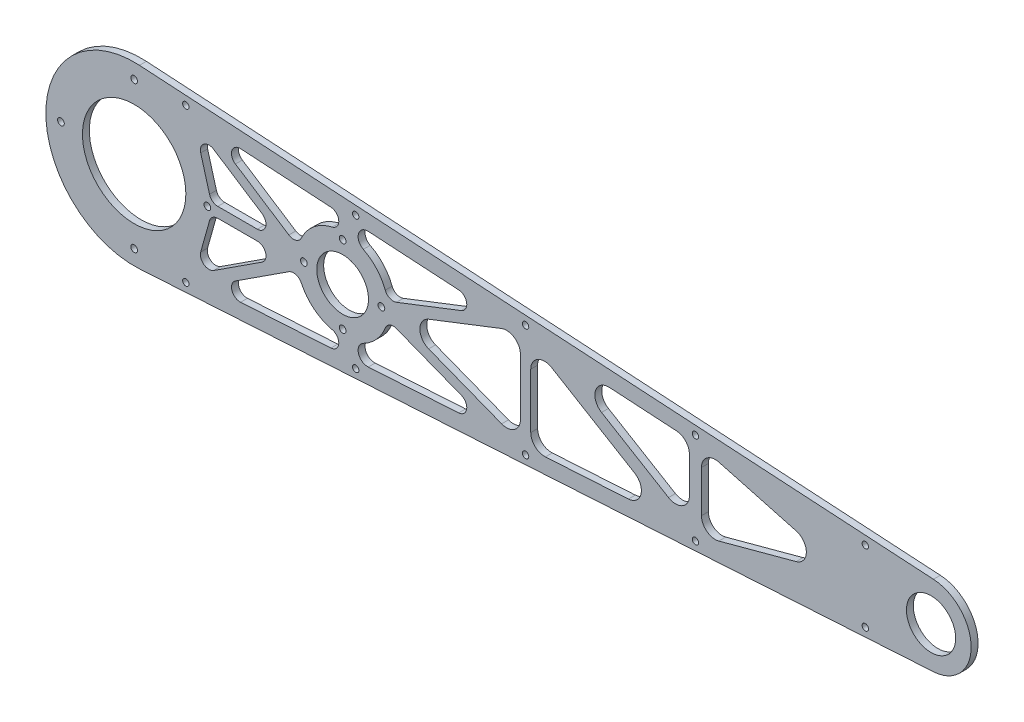
SolidWorks part; units mm, degrees
ref_plane "Front Plane" through (0, 0, 0) normal (0, 0, 1) x (1, 0, 0)
ref_plane "Top Plane" through (0, 0, 0) normal (0, 1, 0) x (1, 0, 0)
ref_plane "Right Plane" through (0, 0, 0) normal (1, 0, 0) x (0, 0, -1)
sketch "Sketch1" plane through (0, 0, 0) normal (0, 0, 1) x (1, 0, 0)
  line L0 (-231.25, 0) -> (231.25, 0) construction
  line L1 (-228.1515, 51.1562) -> (232.6579, 23.2449)
  line L2 (-228.1515, -51.1562) -> (232.6579, -23.2449)
  line L3 (191.25, 20.7438) -> (-201.25, 44.5177) construction
  circle A0 centre (231.25, 0) radius 14.2875
  arc A1 (232.6579, 23.2449) -> (232.6579, -23.2449) centre (231.25, 0) cw
  circle A2 centre (-231.25, 0) radius 42.5 construction
  circle A3 centre (-110.25, 0) radius 22.5 construction
  arc A4 (-228.1515, 51.1562) -> (-228.1515, -51.1562) centre (-231.25, 0) ccw
  circle A5 centre (-231.25, 42.5) radius 1.75 construction
  circle A6 centre (-231.25, 0) radius 30
  circle A7 centre (-110.25, 0) radius 15
  circle A8 centre (231.25, 0) radius 35.306 construction
  circle A9 centre (-201.25, 44.5177) radius 1.85
  circle A10 centre (-102.6633, 38.5462) radius 1.85
  circle A11 centre (-4.0767, 32.5748) radius 1.85
  circle A12 centre (94.51, 26.6034) radius 1.85
  circle A13 centre (193.0966, 20.632) radius 1.85
  circle A14 centre (291.6833, 14.6606) radius 1.85 construction
  circle A15 centre (193.0966, -20.632) radius 1.85
  circle A16 centre (94.51, -26.6034) radius 1.85
  circle A17 centre (-4.0767, -32.5748) radius 1.85
  circle A18 centre (-102.6633, -38.5462) radius 1.85
  circle A19 centre (-201.25, -44.5177) radius 1.85
  point P4 (0, 0)
  point P15 (-231.25, 44.25)
  point P16 (-273.75, 0)
  point P17 (-231.25, 51.25)
  point P18 (-110.25, 22.5)
  point P19 (-231.25, -42.5)
  point P20 (-188.75, 0)
  point P21 (-132.75, 0)
  point P22 (-110.25, -22.5)
  point P23 (-87.75, 0)
  dimension "D2" = 28.575
  dimension "D3" = 85
  dimension "D5" = 45
  dimension "D6" = 3.5
  dimension "D7" = 7
  dimension "D8" = 9
  dimension "D9" = 60
  dimension "D10" = 30
  dimension "D11" = 70.612
  dimension "D13" = 3.7
  dimension "D16" = 6
  dimension "D1" = 462.5
  dimension "D4" = 121
  dimension "D12" = 5
  dimension "D14" = 30
  dimension "D15" = 40
extrude "Boss-Extrude1" add sketch "Sketch1" along normal blind 4
sketch "Sketch4" plane through (0, 0, 4) normal (0, 0, 1) x (1, 0, 0)
  point P0 (-231.25, 42.5)
  point P7 (-188.75, 0)
  point P10 (-132.75, 0)
  point P13 (-110.25, 22.5)
  point P16 (-87.75, 0)
  point P19 (-110.25, -22.5)
  point P24 (-273.75, 0)
  point P28 (-231.25, -42.5)
hole_wizard "M3.5 Clearance Hole1" positions "Sketch4" profile "Sketch6" hole size "M3.5" standard "ANSI Metric" end condition up to next
sketch "Sketch6" plane through (-231.25, 42.5, 4) normal (1, 0, 0) x (0, -1, 0)
  line L0 (0, 0) -> (0, 4)
  line L1 (0, 4) -> (1.95, 4)
  line L2 (1.95, 4) -> (1.95, 0)
  line L5 (1.95, 0) -> (0, 0)
  line L11 (0, -6.35) -> (0, 107.95) construction
  dimension "Thru Hole Dia." = 3.9
  dimension "Thru Hole Depth" = 4
sketch "Sketch7" plane through (0, 0, 4) normal (0, 0, 1) x (1, 0, 0)
  line L0 (94.51, 26.6034) -> (94.51, -26.6034) construction
  line L1 (94.51, -26.6034) -> (193.0966, 0) construction
  line L2 (193.0966, 0) -> (94.51, 26.6034) construction
  line L3 (193.0966, 0) -> (-87.75, 0) construction
  line L4 (193.0966, -20.632) -> (193.0966, 20.632) construction
  line L5 (108.0942, 19.8304) -> (152.959, 7.7237)
  line L6 (152.959, -7.7237) -> (108.0942, -19.8304)
  line L7 (98.01, -12.1067) -> (98.01, 12.1067)
  line L8 (-4.0767, -32.5748) -> (-4.0767, 32.5748) construction
  line L9 (-4.0767, 32.5748) -> (94.51, -26.6034) construction
  line L10 (-4.0767, 32.5748) -> (94.51, 26.6034) construction
  line L11 (-4.0767, -32.5748) -> (94.51, -26.6034) construction
  line L12 (-87.75, 0) -> (-102.6633, 38.5462) construction
  line L13 (-102.6633, 38.5462) -> (-4.0767, 32.5748) construction
  line L14 (-4.0767, 32.5748) -> (-87.75, 0) construction
  line L15 (91.01, -5.7044) -> (91.01, 15.278)
  line L16 (83.4936, 23.2633) -> (44.6155, 25.6182)
  line L17 (40.0145, 10.7737) -> (78.8927, -12.5635)
  line L18 (11.0406, 18.8351) -> (59.2561, -10.107)
  line L19 (55.6224, -24.9515) -> (7.407, -27.8719)
  line L20 (-1.0767, -19.8865) -> (-1.0767, 11.976)
  line L21 (232.6579, 23.2449) -> (-228.1515, 51.1562) construction
  line L22 (-228.1515, -51.1562) -> (232.6579, -23.2449) construction
  line L23 (-7.0767, -16.4882) -> (-7.0767, 16.4882)
  line L24 (-17.979, 23.9432) -> (-60.3314, 7.455)
  line L25 (-60.3314, -7.455) -> (-17.979, -23.9432)
  line L27 (-79.0235, 6.6167) -> (-41.3873, 21.2687)
  line L28 (-42.899, 30.919) -> (-95.3831, 34.0979)
  line L32 (-132.75, 0) -> (-188.75, 0) construction
  line L33 (-188.75, 0) -> (-201.25, 44.5177) construction
  line L34 (-201.25, 44.5177) -> (-132.75, 0) construction
  line L35 (-132.75, 0) -> (-102.6633, 38.5462) construction
  line L36 (-102.6633, 38.5462) -> (-201.25, 44.5177) construction
  line L37 (-172.4851, 29.4014) -> (-141.466, 9.2423)
  line L39 (-117.0641, 35.4112) -> (-169.4581, 38.5847)
  line L40 (-192.6227, 24.8897) -> (-187.5008, 6.6483)
  line L41 (-182.6869, 3) -> (-159.7406, 3)
  line L42 (-157.016, 12.1924) -> (-185.0842, 30.4338)
  line L44 (-117.0641, -35.4112) -> (-169.4581, -38.5847)
  line L45 (-172.4851, -29.4014) -> (-141.466, -9.2423)
  line L46 (-157.016, -12.1924) -> (-185.0842, -30.4338)
  line L47 (-192.6227, -24.8897) -> (-187.5008, -6.6483)
  line L48 (-182.6869, -3) -> (-159.7406, -3)
  line L50 (-42.899, -30.919) -> (-95.3831, -34.0979)
  line L51 (-79.0235, -6.6167) -> (-41.3873, -21.2687)
  line L52 (-102.6633, -38.5462) -> (-110.25, -22.5) construction
  line L53 (-112.9575, -28.4712) -> (-105.7377, -43.7416) construction
  line L54 (-100.7324, -30.9326) -> (-94.9842, -43.0903) construction
  arc A0 (152.959, 7.7237) -> (152.959, -7.7237) centre (150.8748, 0) cw
  arc A1 (108.0942, -19.8304) -> (98.01, -12.1067) centre (106.01, -12.1067) cw
  arc A2 (108.0942, 19.8304) -> (98.01, 12.1067) centre (106.01, 12.1067) ccw
  arc A3 (91.01, 15.278) -> (83.4936, 23.2633) centre (83.01, 15.278) ccw
  arc A4 (44.6155, 25.6182) -> (40.0145, 10.7737) centre (44.1318, 17.6328) ccw
  arc A5 (91.01, -5.7044) -> (78.8927, -12.5635) centre (83.01, -5.7044) cw
  arc A6 (59.2561, -10.107) -> (55.6224, -24.9515) centre (55.1388, -16.9661) cw
  arc A7 (7.407, -27.8719) -> (-1.0767, -19.8865) centre (6.9233, -19.8865) cw
  arc A8 (11.0406, 18.8351) -> (-1.0767, 11.976) centre (6.9233, 11.976) ccw
  arc A9 (-7.0767, -16.4882) -> (-17.979, -23.9432) centre (-15.0767, -16.4882) cw
  arc A10 (-7.0767, 16.4882) -> (-17.979, 23.9432) centre (-15.0767, 16.4882) ccw
  arc A11 (-60.3314, 7.455) -> (-60.3314, -7.455) centre (-57.4292, 0) ccw
  arc A12 (-41.3873, 21.2687) -> (-42.899, 30.919) centre (-43.2013, 25.9281) ccw
  arc A18 (-172.4851, 29.4014) -> (-169.4581, 38.5847) centre (-169.7604, 33.5938) cw
  arc A21 (-159.7406, 3) -> (-157.016, 12.1924) centre (-159.7406, 8) ccw
  arc A22 (-187.5008, 6.6483) -> (-182.6869, 3) centre (-182.6869, 8) ccw
  arc A23 (-192.6227, 24.8897) -> (-185.0842, 30.4338) centre (-187.8089, 26.2413) cw
  arc A26 (-172.4851, -29.4014) -> (-169.4581, -38.5847) centre (-169.7604, -33.5938) ccw
  arc A27 (-192.6227, -24.8897) -> (-185.0842, -30.4338) centre (-187.8089, -26.2413) ccw
  arc A28 (-187.5008, -6.6483) -> (-182.6869, -3) centre (-182.6869, -8) cw
  arc A29 (-159.7406, -3) -> (-157.016, -12.1924) centre (-159.7406, -8) cw
  circle A30 centre (-110.25, 0) radius 15 construction
  circle A31 centre (-110.25, 0) radius 15 construction
  circle A32 centre (-110.25, 0) radius 22.5 construction
  arc A34 (-85.5061, 9.4862) -> (-98.2334, 23.6189) centre (-110.25, 0) ccw
  arc A37 (-85.5061, 9.4862) -> (-79.0235, 6.6167) centre (-80.8374, 11.276) ccw
  arc A38 (-41.3873, -21.2687) -> (-42.899, -30.919) centre (-43.2013, -25.9281) cw
  arc A39 (-95.3831, -34.0979) -> (-98.2334, -23.6189) centre (-95.7185, -28.562) cw
  arc A40 (-134.2189, 11.3023) -> (-116.2553, 25.8106) centre (-110.25, 0) cw
  arc A41 (-85.5061, -9.4862) -> (-98.2334, -23.6189) centre (-110.25, 0) cw
  arc A42 (-85.5061, -9.4862) -> (-79.0235, -6.6167) centre (-80.8374, -11.276) cw
  arc A43 (-117.0641, 35.4112) -> (-116.2553, 25.8106) centre (-117.3584, 30.552) cw
  arc A44 (-134.2189, 11.3023) -> (-141.466, 9.2423) centre (-138.7414, 13.4348) cw
  arc A45 (-117.0641, -35.4112) -> (-116.2553, -25.8106) centre (-117.3584, -30.552) ccw
  arc A46 (-134.2189, -11.3023) -> (-116.2553, -25.8106) centre (-110.25, 0) ccw
  arc A47 (-134.2189, -11.3023) -> (-141.466, -9.2423) centre (-138.7414, -13.4348) ccw
  arc A48 (-95.3831, 34.0979) -> (-98.2334, 23.6189) centre (-95.7185, 28.562) ccw
  point P36 (181.5816, 0)
  point P59 (-79.4807, 0)
  point P102 (-112.9575, -28.4712)
  dimension "D8" = 8
  dimension "D11" = 5
  dimension "D12" = 5
  dimension "D18" = 5
  dimension "D19" = 5
  dimension "D10" = 4
  dimension "D21" = 5
  dimension "D1" = 3
  dimension "D2" = 7
  dimension "D3" = 8
  dimension "D4" = 8
  dimension "D5" = 8
  dimension "D6" = 6
  dimension "D7" = 6
  dimension "D9" = 8
  dimension "D13" = 8
  dimension "D14" = 5
  dimension "D15" = 6
  dimension "D16" = 3
  dimension "D17" = 6
extrude "Cut-Extrude1" cut sketch "Sketch7" against normal blind 10
